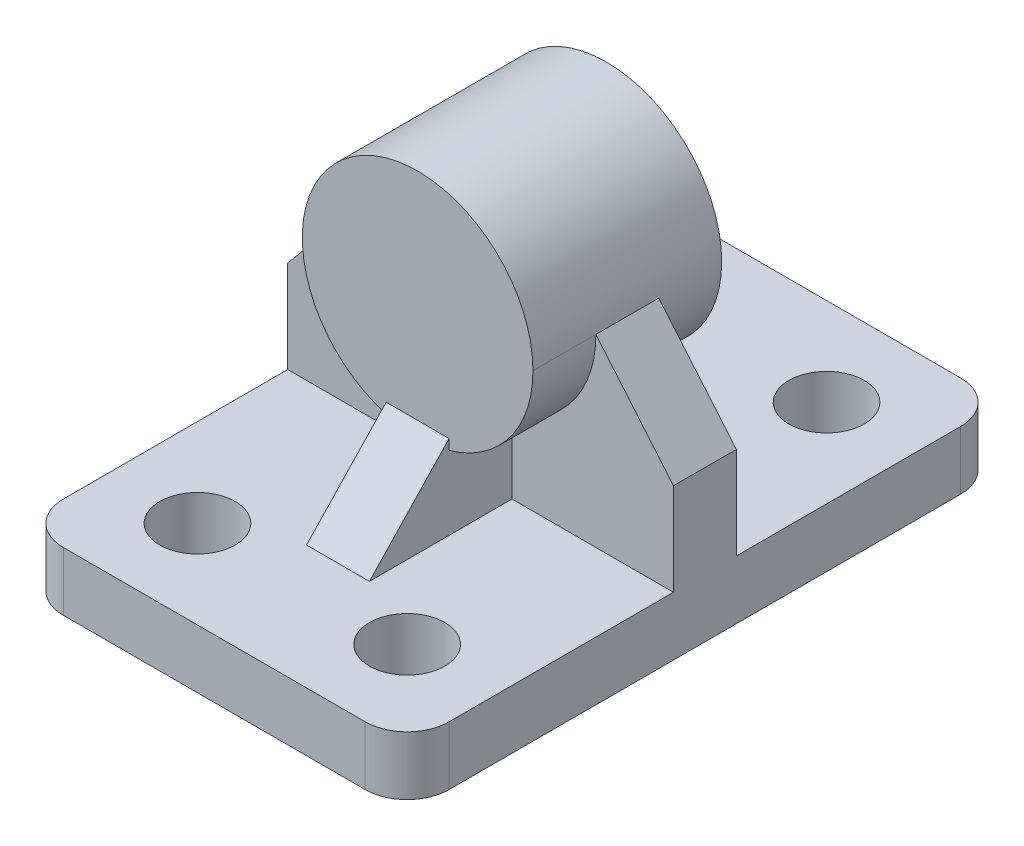
SolidWorks part; units mm, degrees
ref_plane "Front Plane" through (0, 0, 0) normal (0, 0, 1) x (1, 0, 0)
ref_plane "Top Plane" through (0, 0, 0) normal (0, 1, 0) x (1, 0, 0)
ref_plane "Right Plane" through (0, 0, 0) normal (1, 0, 0) x (0, 0, -1)
sketch "Sketch1" plane through (0, 0, 0) normal (1, 0, 0) x (0, 0, -1)
  line L0 (0, 0) -> (0, 76.3552) construction
  line L1 (-71, 14) -> (71, 14)
  line L2 (-71, 14) -> (-71, 0)
  line L3 (-71, 0) -> (71, 0)
  line L4 (71, 14) -> (71, 0)
  dimension "D1" = 142
  dimension "D2" = 14
extrude "Boss-Extrude1" add sketch "Sketch1" along normal blind 46 and the other way blind 46
sketch "Sketch2" plane through (0, 0, 0) normal (0, 0, 1) x (1, 0, 0)
  circle A0 centre (0, 58) radius 27.5
  dimension "D2" = 55
  dimension "D1" = 58
extrude "Boss-Extrude2" add sketch "Sketch2" along normal blind 22.5 and the other way blind 22.5 separate body
sketch "Sketch3" plane through (0, 0, 0) normal (0, 0, 1) x (1, 0, 0)
  line L0 (-46, 36) -> (-27.5, 58)
  line L1 (-46, 36) -> (-46, 14)
  line L2 (0, -47.025) -> (0, 47.025) construction
  line L3 (46, 36) -> (46, 14)
  line L4 (46, 36) -> (27.5, 58)
  line L5 (-27.5, 58) -> (27.5, 58)
  line L6 (-46, 14) -> (46, 14)
  line L7 (-27.5, 58) -> (27.5, 58) construction
  circle A1 centre (0, 58) radius 27.5 construction
  dimension "D1" = 36
extrude "Boss-Extrude3" add sketch "Sketch3" along normal blind 7.5 and the other way blind 7.5 contours L4 L5 L0 L1 L6 L3
sketch "Sketch4" plane through (0, 0, 0) normal (1, 0, 0) x (0, 0, -1)
  line L0 (-41.5, 14) -> (-22.5, 34)
  line L1 (-7.5, 14) -> (-71, 14) construction
  line L2 (-22.5, 34) -> (-22.5, 31.5)
  line L3 (-22.5, 31.5) -> (-7.5, 31.5)
  line L4 (-7.5, 31.5) -> (-7.5, 14)
  line L5 (-7.5, 14) -> (-41.5, 14)
  line L6 (-7.5, 36) -> (-7.5, 14) construction
  line L7 (-22.5, 85.5) -> (-22.5, 30.5) construction
  line L9 (7.5, 58) -> (-7.5, 58) construction
  point P11 (0, 0)
  dimension "D1" = 34
  dimension "D2" = 20
  dimension "D3" = 26.5
extrude "Boss-Extrude7" add sketch "Sketch4" along normal blind 7.5 and the other way blind 7.5 contours L0 L2 L3 L4 L5
hole_wizard "Hole1" positions "Sketch7" profile "Sketch8" legacy end condition through all
sketch "Sketch7" plane through (0, 14, 0) normal (0, 1, 0) x (1, 0, 0)
  point P0 (25, -50)
  point P2 (-25, -50)
  point P4 (-25, 50)
  point P6 (25, 50)
  point P9 (0, 0)
  point P10 (0, 0)
  point P11 (0, 0)
  point P12 (0, 0)
  point P13 (0, 0)
  dimension "D1" = 100
  dimension "D2" = 50
  dimension "D3" = 50
  dimension "D4" = 25
sketch "Sketch8" plane through (25, 14, 50) normal (1, 0, 0) x (0, 0, 1)
  line L0 (0, 0) -> (0, 14)
  line L1 (0, 14) -> (9, 14)
  line L2 (9, 14) -> (9, 0)
  line L3 (9, 0) -> (0, 0)
  line L4 (0, 110) -> (0, -10) construction
  dimension "Diameter" = 18
  dimension "Depth" = 14
fillet "Fillet1" radius 10 4 edges at (-46, 7, -71) (46, 7, -71) (46, 7, 71) (-46, 7, 71)
